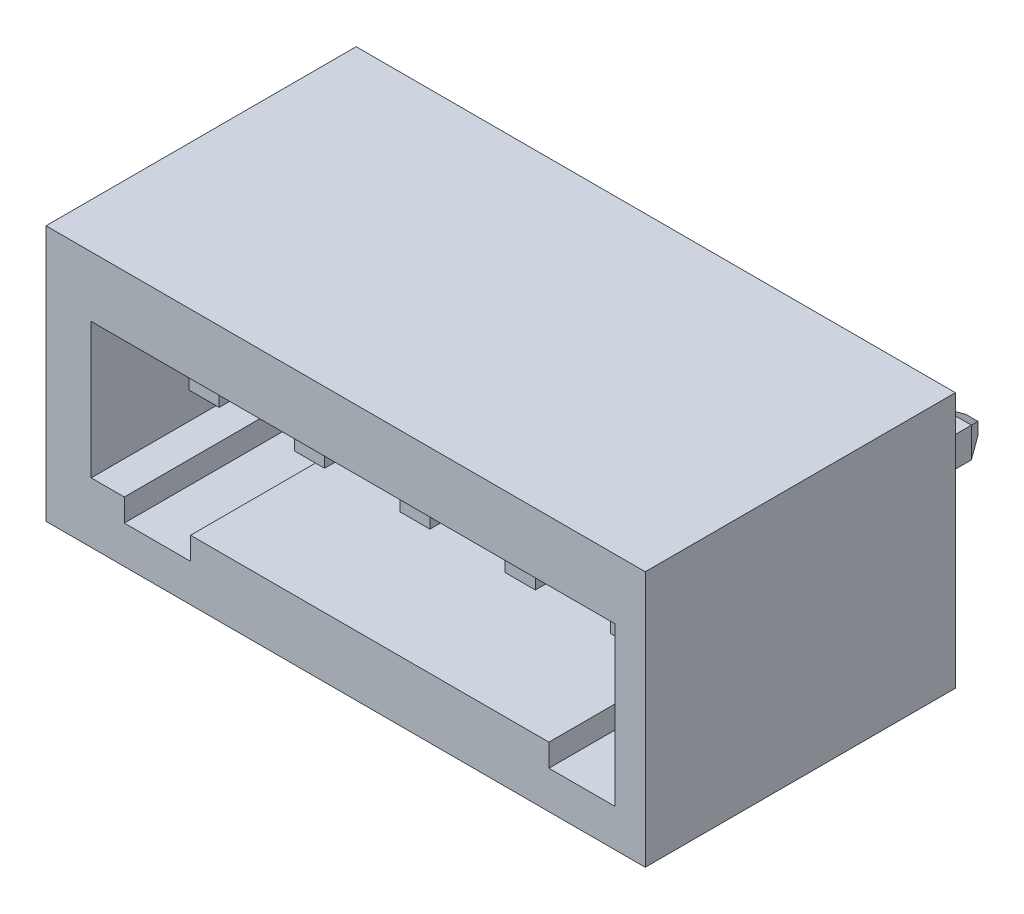
SolidWorks part; units mm, degrees
other "Детальный элемент1"
ref_plane "Спереди" through (0, 0, 0) normal (0, 0, 1) x (1, 0, 0)
ref_plane "Сверху" through (0, 0, 0) normal (0, 1, 0) x (1, 0, 0)
ref_plane "Справа" through (0, 0, 0) normal (1, 0, 0) x (0, 0, -1)
ref_axis "Ось1" through (80.9, 0, 0) along (-1, 0, 0)
sketch "Эскиз1" plane through (0, 0, 0) normal (0, 0, 1) x (1, 0, 0)
  line L0 (50, 0) -> (-50, 0) construction
  line L1 (-7.5, -0.5) -> (-6.5, -0.5)
  line L2 (-7.5, -0.5) -> (-7.5, 0.5)
  line L3 (-7.5, 0.5) -> (-6.5, 0.5)
  line L4 (-6.5, -0.5) -> (-6.5, 0.5)
  line L5 (-7.5, -0.5) -> (-6.5, 0.5) construction
  line L6 (-7.5, 0.5) -> (-6.5, -0.5) construction
  point P0 (-7, 0)
  dimension "D1" = 7
  dimension "D2" = 1
  dimension "D3" = 1
extrude "Бобышка-Вытянуть1" add sketch "Эскиз1" along normal blind 8 and the other way blind 3.5
chamfer "Фаска1" distance 0.3 angle 60 4 edges at (-7, -0.5, -3.5) (-7.5, 0, -3.5) (-7, 0.5, -3.5) (-6.5, 0, -3.5) first distance on face at (-7, 0, -3.5)
pattern_linear "Линейный массив1" count 5 spacing 3.5 along (1, 0, 0) of bodies 107
sketch "Эскиз3" plane through (0, 0, 0) normal (0, 0, 1) x (1, 0, 0)
  line L0 (0, -50) -> (0, 50) construction
  line L1 (9.95, 4.15) -> (-9.95, 4.15)
  line L2 (9.95, 4.15) -> (9.95, -4.35)
  line L3 (9.95, -4.35) -> (-9.95, -4.35)
  line L4 (-9.95, 4.15) -> (-9.95, -4.35)
  line L5 (9.95, 4.15) -> (-9.95, -4.35) construction
  line L6 (9.95, -4.35) -> (-9.95, 4.15) construction
  point P0 (0, -0.1)
  dimension "D1" = 8.5
  dimension "D2" = 19.9
  dimension "D3" = 4.35
extrude "Бобышка-Вытянуть2" add sketch "Эскиз3" along normal blind 10.3 separate body
shell "Оболочка1" thickness 2 removed face at (0, -0.1, 10.3)
sketch "Эскиз4" plane through (0, 0, 10.3) normal (0, 0, 1) x (1, 0, 0)
  line L0 (-8.45, -2.35) -> (8.95, -2.35) construction
  line L1 (-7.35, -2.35) -> (-5.15, -2.35)
  line L2 (-7.35, -2.35) -> (-7.35, -3.1)
  line L3 (-7.35, -3.1) -> (-5.15, -3.1)
  line L4 (-5.15, -2.35) -> (-5.15, -3.1)
  line L5 (-9.95, 4.15) -> (-9.95, -4.35) construction
  line L6 (6.75, -2.35) -> (8.95, -2.35)
  line L7 (6.75, -2.35) -> (6.75, -3.1)
  line L8 (6.75, -3.1) -> (8.95, -3.1)
  line L9 (8.95, -2.35) -> (8.95, -3.1)
  line L10 (9.95, -4.35) -> (9.95, 4.15) construction
  dimension "D1" = 2.2
  dimension "D2" = 0.75
  dimension "D3" = 4.8
  dimension "D4" = 3.2
extrude "Вырез-Вытянуть1" cut sketch "Эскиз4" against normal up to surface (8.8 mm away) up to face at (0.25, -0.1, 1.5)
